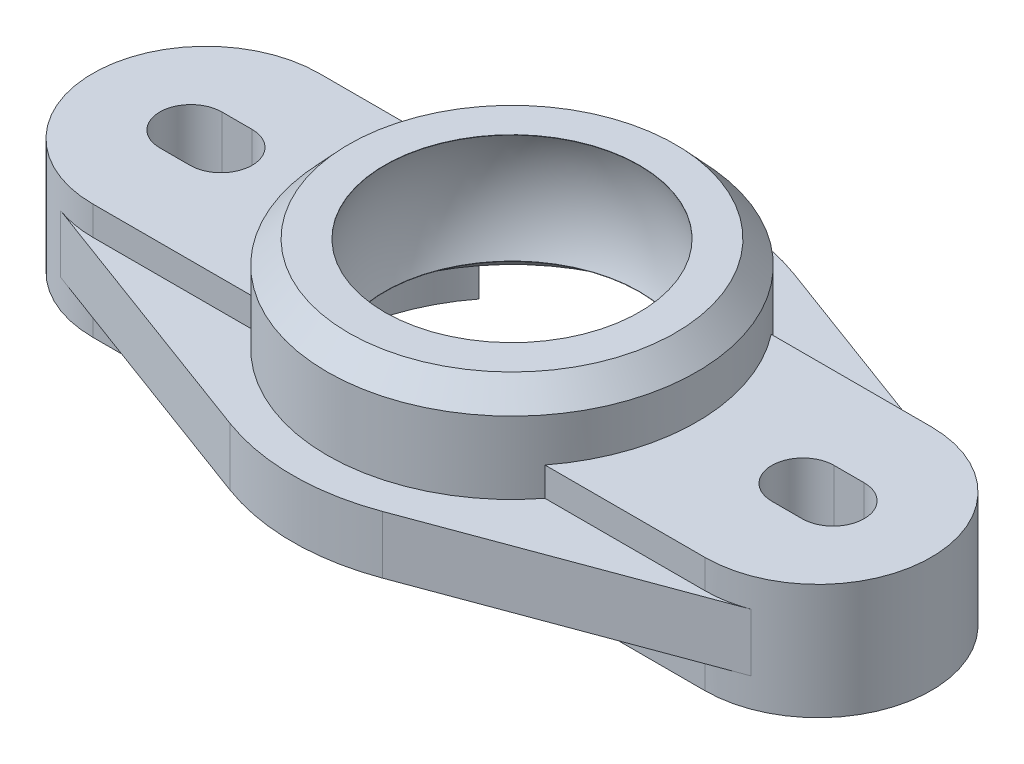
SolidWorks part; units mm, degrees
ref_plane "Front Plane" through (0, 0, 0) normal (0, 0, 1) x (1, 0, 0)
ref_plane "Top Plane" through (0, 0, 0) normal (0, 1, 0) x (1, 0, 0)
ref_plane "Right Plane" through (0, 0, 0) normal (1, 0, 0) x (0, 0, -1)
sketch "Sketch1" plane through (0, 0, 0) normal (0, 1, 0) x (1, 0, 0)
  line L0 (-26.5049, 0) -> (26.5049, 0) construction
  line L1 (-26.5049, 9.7993) -> (26.5049, 9.7993)
  line L2 (-26.5049, -9.7993) -> (26.5049, -9.7993)
  line L3 (25.1968, 0) -> (27.813, 0) construction
  line L4 (25.1968, 2.6924) -> (27.813, 2.6924)
  line L5 (25.1968, -2.6924) -> (27.813, -2.6924)
  line L6 (-27.813, 0) -> (-25.1968, 0) construction
  line L7 (-27.813, 2.6924) -> (-25.1968, 2.6924)
  line L8 (-27.813, -2.6924) -> (-25.1968, -2.6924)
  line L9 (-36.3042, 0) -> (36.3042, 0) construction
  line L10 (-30.5054, 0) -> (-22.5044, 0) construction
  arc A0 (-26.5049, 9.7993) -> (-26.5049, -9.7993) centre (-26.5049, 0) ccw
  arc A1 (26.5049, -9.7993) -> (26.5049, 9.7993) centre (26.5049, 0) ccw
  arc A2 (25.1968, 2.6924) -> (25.1968, -2.6924) centre (25.1968, 0) ccw
  arc A3 (27.813, -2.6924) -> (27.813, 2.6924) centre (27.813, 0) ccw
  arc A4 (-27.813, 2.6924) -> (-27.813, -2.6924) centre (-27.813, 0) ccw
  arc A5 (-25.1968, -2.6924) -> (-25.1968, 2.6924) centre (-25.1968, 0) ccw
  point P3 (0, 0)
  point P10 (26.5049, 0)
  point P15 (-26.5049, 0)
  dimension "D2" = 9.7993
  dimension "D4" = 8.001
  dimension "D3" = 2.6924
  dimension "D1" = 53.0098
extrude "Boss-Extrude1" add sketch "Sketch1" along normal mid plane 10
sketch "Sketch2" plane through (0, 0, 0) normal (0, 1, 0) x (1, 0, 0)
  line L0 (-29.9063, 9.1901) -> (-6.5946, 17.818)
  line L1 (6.5946, 17.818) -> (29.9063, 9.1901)
  line L2 (0, 0) -> (0, 18.9992) construction
  line L3 (-36.3042, 0) -> (36.3042, 0) construction
  line L4 (6.5946, -17.818) -> (29.9063, -9.1901)
  line L5 (-29.9063, -9.1901) -> (-6.5946, -17.818)
  line L6 (0, -18.9992) -> (0, 18.9992) construction
  line L7 (-25.1968, 2.6924) -> (-27.813, 2.6924) construction
  line L8 (-25.1968, 2.6924) -> (-27.813, 2.6924)
  line L9 (-27.813, -2.6924) -> (-25.1968, -2.6924) construction
  line L10 (27.813, 2.6924) -> (25.1968, 2.6924) construction
  line L11 (25.1968, -2.6924) -> (27.813, -2.6924) construction
  line L12 (-27.813, -2.6924) -> (-25.1968, -2.6924)
  line L13 (27.813, 2.6924) -> (25.1968, 2.6924)
  line L14 (25.1968, -2.6924) -> (27.813, -2.6924)
  arc A0 (-26.5049, 9.7993) -> (-26.5049, -9.7993) centre (-26.5049, 0) ccw construction
  arc A1 (26.5049, -9.7993) -> (26.5049, 9.7993) centre (26.5049, 0) ccw construction
  arc A2 (-29.9063, 9.1901) -> (-29.9063, -9.1901) centre (-26.5049, 0) ccw
  arc A3 (29.9063, -9.1901) -> (29.9063, 9.1901) centre (26.5049, 0) ccw
  arc A4 (-6.5946, 17.818) -> (6.5946, 17.818) centre (0, 0) cw
  arc A5 (-6.5946, -17.818) -> (6.5946, -17.818) centre (0, 0) ccw
  arc A6 (-25.1968, -2.6924) -> (-25.1968, 2.6924) centre (-25.1968, 0) ccw construction
  arc A7 (-27.813, 2.6924) -> (-27.813, -2.6924) centre (-27.813, 0) ccw construction
  arc A8 (27.813, -2.6924) -> (27.813, 2.6924) centre (27.813, 0) ccw construction
  arc A9 (25.1968, 2.6924) -> (25.1968, -2.6924) centre (25.1968, 0) ccw construction
  arc A10 (-25.1968, -2.6924) -> (-25.1968, 2.6924) centre (-25.1968, 0) ccw
  arc A11 (-27.813, 2.6924) -> (-27.813, -2.6924) centre (-27.813, 0) ccw
  arc A12 (27.813, -2.6924) -> (27.813, 2.6924) centre (27.813, 0) ccw
  arc A13 (25.1968, 2.6924) -> (25.1968, -2.6924) centre (25.1968, 0) ccw
  dimension "D2" = 18.9992
  dimension "D1" = 37.9984
extrude "Boss-Extrude2" add sketch "Sketch2" along normal mid plane 5.0013
sketch "Sketch4" plane through (0, 2.5006, 0) normal (0, 1, 0) x (1, 0, 0)
  circle A0 centre (0, 0) radius 16.002
  dimension "D1" = 32.004
extrude "Boss-Extrude3" add sketch "Sketch4" along normal blind 8.2499
sketch "Sketch5" plane through (0, 10.7505, 0) normal (0, 1, 0) x (1, 0, 0)
  circle A0 centre (0, 0) radius 11.0305
  dimension "D1" = 22.0609
extrude "Cut-Extrude1" cut sketch "Sketch5" against normal through all
sketch "Sketch6" plane through (0, -5, 0) normal (0, -1, 0) x (1, 0, 0)
  circle A0 centre (0, 0) radius 15.9995
  dimension "D1" = 31.9989
extrude "Cut-Extrude2" cut sketch "Sketch6" against normal up to surface (2.4994 mm away) up to face at (0, -2.5006, 11.991)
sketch "Sketch7" plane through (0, 0, 0) normal (0, 0, 1) x (1, 0, 0)
  line L0 (12.6474, -2.5006) -> (15.9995, -2.5006) construction
  line L1 (12.6474, -2.5006) -> (15.9995, -2.5006)
  line L2 (12.5374, -2.5006) -> (12.6474, -2.5006)
  line L3 (15.9995, -2.5006) -> (12.5374, 1.2484)
  line L7 (12.5374, -2.5006) -> (12.5374, 1.2484)
  line L9 (-9.5235, -2.5006) -> (12.5374, -2.5006) construction
  dimension "D1" = 3.749
  dimension "D2" = 3.462
revolve "Cut-Revolve1" cut sketch "Sketch7" angle 360 about axis through (0, 2.5006, 0) along (0, -1, 0)
sketch "Sketch8" plane through (0, -2.5006, 0) normal (0, -1, 0) x (1, 0, 0)
  circle A1 centre (0, 0) radius 12.5374
  circle A2 centre (0, 0) radius 12.5374
  dimension "D1" = 0
extrude "Cut-Extrude3" cut sketch "Sketch8" against normal offset from surface (3.7516 mm away) 9.4996 up to face at (0, 10.7505, 11.0305)
chamfer "Chamfer2" distance 1.999 distance2 1.8567 1 edges at (0, 10.7505, 16.002) first distance on face at (0, 10.7505, 16.002)
ref_plane "Plane1" through (0, 6.0007, 0) normal (0, 1, 0) x (1, 0, 0)
sketch "Sketch9" plane through (0, 6.0007, 0) normal (0, 1, 0) x (1, 0, 0)
  line L0 (0, 22.1822) -> (0, -25.7103) construction
  line L1 (0, 12.0002) -> (0, -12.0002)
  arc A0 (0, -12.0002) -> (0, 12.0002) centre (0, 0) ccw
  dimension "D1" = 24.0005
revolve "Cut-Revolve2" cut sketch "Sketch9" angle 360 about L0
